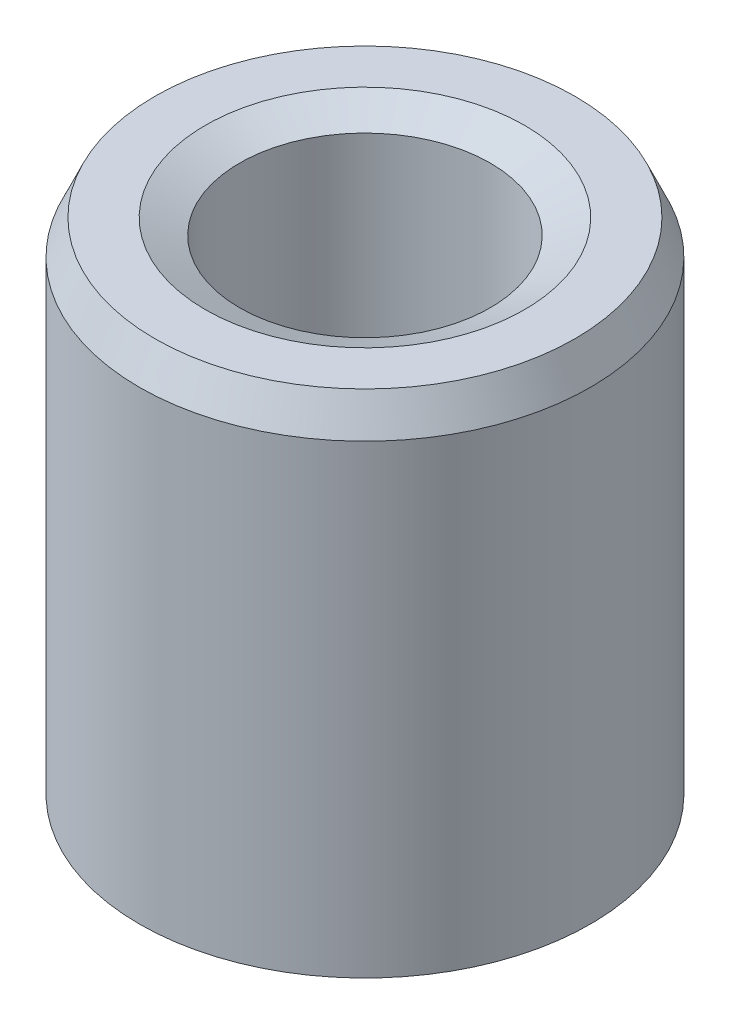
SolidWorks part; units mm, degrees
ref_plane "Front Plane" through (0, 0, 0) normal (0, 0, 1) x (1, 0, 0)
ref_plane "Top Plane" through (0, 0, 0) normal (0, 1, 0) x (1, 0, 0)
ref_plane "Right Plane" through (0, 0, 0) normal (1, 0, 0) x (0, 0, -1)
sketch "Sketch1" plane through (0, 0, 0) normal (0, 1, 0) x (1, 0, 0)
  circle A0 centre (0, 0) radius 5
  dimension "SLEEVE_OD" = 10
extrude "Boss-Extrude1" add sketch "Sketch1" along normal blind 11.4106
sketch "Sketch2" plane through (0, 0, 0) normal (0, 1, 0) x (1, 0, 0)
  circle A0 centre (0, 0) radius 2.779
  dimension "BORE_D" = 5.558
extrude "Cut-Extrude1" cut sketch "Sketch2" along normal through all
chamfer "Chamfer1" distance 0.7605 angle 24.331 4 edges at (0, 11.4106, 2.779) (0, 0, 2.779) (0, 0, 5) (0, 11.4106, 5) first distance on face at (0, 11.4106, 2.779) first distance on face at (0, 0, 2.779) first distance on face at (0, 11.4106, 5)
